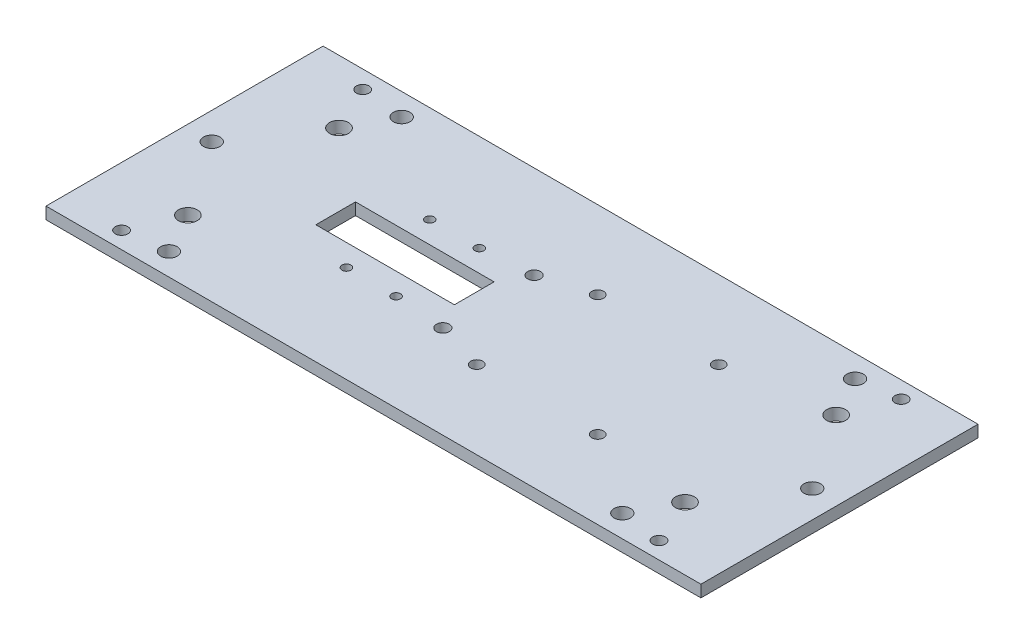
SolidWorks part; units mm, degrees
material "Thornel VCB-20 Carbon Cloth"
ref_plane "Front Plane" through (0, 0, 0) normal (0, 0, 1) x (1, 0, 0)
ref_plane "Top Plane" through (0, 0, 0) normal (0, 1, 0) x (1, 0, 0)
ref_plane "Right Plane" through (0, 0, 0) normal (1, 0, 0) x (0, 0, -1)
sketch "Sketch1" plane through (0, 0, 0) normal (0, 1, 0) x (1, 0, 0)
  line L0 (82.55, -34.925) -> (82.55, 34.925)
  line L1 (82.55, -34.925) -> (-82.55, -34.925)
  line L2 (82.55, 34.925) -> (-82.55, 34.925)
  line L3 (-82.55, -34.925) -> (-82.55, 34.925)
  line L4 (82.55, -34.925) -> (-82.55, 34.925) construction
  line L5 (82.55, 34.925) -> (-82.55, -34.925) construction
  point P1 (0, 0)
  dimension "D1" = 165.1
  dimension "D2" = 69.85
extrude "Boss-Extrude1" add sketch "Sketch1" along normal blind 3
sketch "Sketch6" plane through (0, 0, 0) normal (0, -1, 0) x (1, 0, 0)
  line L0 (-82.55, -34.925) -> (-82.55, 34.925) construction
  line L1 (-44.45, 5) -> (-9.525, 5)
  line L2 (-44.45, 5) -> (-44.45, -5)
  line L3 (-44.45, -5) -> (-9.525, -5)
  line L4 (-9.525, 5) -> (-9.525, -5)
  line L5 (-5.925, -11.501) -> (-63.925, -11.501) construction
  line L6 (-5.925, -11.501) -> (-5.925, 11.501) construction
  line L7 (-5.925, 11.501) -> (-63.925, 11.501) construction
  line L8 (-63.925, -11.501) -> (-63.925, 11.501) construction
  line L9 (-5.925, -11.501) -> (-63.925, 11.501) construction
  line L10 (-5.925, 11.501) -> (-63.925, -11.501) construction
  circle A0 centre (6.35, 15.25) radius 1.5
  circle A1 centre (36.85, 15.25) radius 1.5
  circle A2 centre (6.35, -15.25) radius 1.5
  circle A3 centre (36.85, -15.25) radius 1.5
  circle A4 centre (-63.925, 11.501) radius 1.625 construction
  circle A5 centre (-5.925, 11.501) radius 1.625
  circle A6 centre (-5.925, -11.501) radius 1.625
  circle A7 centre (-63.925, -11.501) radius 1.625 construction
  point P8 (-9.525, 0)
  point P9 (-22.225, 0)
  point P16 (0, 0)
  point P18 (-34.925, 0)
  dimension "D5" = 3
  dimension "D6" = 3
  dimension "D7" = 3
  dimension "D8" = 3
  dimension "D18" = 3.25
  dimension "D1" = 34.925
  dimension "D2" = 10
  dimension "D3" = 38.1
  dimension "D4" = 30.5
  dimension "D9" = 30.5
  dimension "D10" = 30.5
  dimension "D11" = 15.25
  dimension "D12" = 6.35
  dimension "D13" = 15.25
  dimension "D14" = 15.25
  dimension "D15" = 15.25
  dimension "D16" = 23.002
  dimension "D17" = 58
  dimension "D19" = 47.625
  dimension "D20" = 0
extrude "Cut-Extrude1" cut sketch "Sketch6" against normal up to next contours A4 | L4 L1 L2 L3 A4 | A6 | A2 | A3 | A1 | A0 | A7 | A5 region at (-26.9875, 0, 0) region at (6.35, 0, 15.25) region at (36.85, 0, 15.25) region at (6.35, 0, -15.25) region at (36.85, 0, -15.25) region at (-5.925, 0, -11.501)
sketch "Sketch7" plane through (0, 3, 0) normal (0, 1, 0) x (1, 0, 0)
  line L0 (-82.55, 34.925) -> (-82.55, -34.925) construction
  line L1 (82.55, -34.925) -> (82.55, 34.925) construction
  line L2 (-82.55, -34.925) -> (82.55, -34.925) construction
  line L3 (82.55, 34.925) -> (-82.55, 34.925) construction
  circle A0 centre (-77.47, 29.845) radius 1.5
  circle A1 centre (-77.47, -29.845) radius 1.5
  circle A2 centre (77.47, -29.845) radius 1.5
  circle A3 centre (77.47, 29.845) radius 1.5
  dimension "D9" = 3
  dimension "D10" = 3
  dimension "D11" = 3
  dimension "D12" = 3
  dimension "D1" = 5.08
  dimension "D2" = 5.08
  dimension "D3" = 5.08
  dimension "D4" = 5.08
  dimension "D5" = 5.08
  dimension "D6" = 5.08
  dimension "D7" = 5.08
  dimension "D8" = 5.08
sketch "Sketch8" plane through (0, 3, 0) normal (0, 1, 0) x (1, 0, 0)
  line L0 (-82.55, -34.925) -> (82.55, -34.925) construction
  line L1 (-82.55, 34.925) -> (-82.55, -34.925) construction
  line L2 (82.55, -34.925) -> (82.55, 34.925) construction
  line L3 (82.55, 34.925) -> (-82.55, 34.925) construction
  circle A0 centre (-62.6618, -19.05) radius 2.3813
  circle A1 centre (-62.6618, 19.05) radius 2.3813
  circle A2 centre (62.6618, 19.05) radius 2.3813
  circle A3 centre (62.6618, -19.05) radius 2.3813
  dimension "D1" = 4.7625
  dimension "D4" = 4.7625
  dimension "D5" = 4.7625
  dimension "D6" = 4.7625
  dimension "D2" = 15.875
  dimension "D3" = 19.8882
  dimension "D7" = 19.8882
  dimension "D8" = 19.8882
  dimension "D9" = 19.8882
  dimension "D10" = 15.875
  dimension "D11" = 15.875
  dimension "D12" = 15.875
extrude "Cut-Extrude3" cut sketch "Sketch8" against normal up to next
sketch "Sketch9" plane through (0, 3, 0) normal (0, 1, 0) x (1, 0, 0)
  line L0 (-82.55, 34.925) -> (-82.55, -34.925) construction
  line L1 (82.55, -34.925) -> (82.55, 34.925) construction
  circle A0 centre (-75.692, 0) radius 2.0828
  circle A1 centre (75.692, 0) radius 2.0828
  dimension "D1" = 6.858
  dimension "D2" = 6.858
extrude "Cut-Extrude5" cut sketch "Sketch9" against normal blind 5.08
sketch "Sketch10" plane through (0, 3, 0) normal (0, 1, 0) x (1, 0, 0)
  line L0 (-82.55, -34.925) -> (82.55, -34.925) construction
  line L1 (82.55, 34.925) -> (-82.55, 34.925) construction
  circle A0 centre (0, -29.337) radius 2.0828
  circle A1 centre (0, 29.337) radius 2.0828
  circle A2 centre (57.15, -29.337) radius 2.0828
  circle A3 centre (57.15, 29.337) radius 2.0828
  circle A4 centre (-57.15, -29.337) radius 2.0828
  circle A5 centre (-57.15, 29.337) radius 2.0828
  dimension "D1" = 5.588
  dimension "D2" = 5.588
  dimension "D3" = 2
  dimension "D4" = 2
extrude "Cut-Extrude6" cut sketch "Sketch10" against normal blind 5.08 contours A5 | A2 | A3 | A4 region at (57.15, 3, 29.337) region at (57.15, 3, -29.337) region at (-57.15, 3, 29.337) region at (-57.15, 3, -29.337)
sketch "Sketch11" plane through (0, 3, 0) normal (0, 1, 0) x (1, 0, 0)
  line L1 (-18.7375, 10.5) -> (-31.2375, 10.5) construction
  line L2 (-18.7375, 10.5) -> (-18.7375, -10.5) construction
  line L3 (-18.7375, -10.5) -> (-31.2375, -10.5) construction
  line L4 (-31.2375, 10.5) -> (-31.2375, -10.5) construction
  line L5 (-18.7375, 10.5) -> (-31.2375, -10.5) construction
  line L6 (-18.7375, -10.5) -> (-31.2375, 10.5) construction
  line L7 (-9.525, 5) -> (-44.45, 5) construction
  circle A0 centre (-31.2375, 10.5) radius 1.125
  circle A1 centre (-18.7375, 10.5) radius 1.125
  circle A2 centre (-18.7375, -10.5) radius 1.125
  circle A3 centre (-31.2375, -10.5) radius 1.125
  point P0 (-24.9875, 0)
  point P9 (-26.9875, 5)
  dimension "D4" = 2.25
  dimension "D5" = 2.25
  dimension "D6" = 2.25
  dimension "D7" = 2.25
  dimension "D1" = 12.5
  dimension "D2" = 21
  dimension "D3" = 2
extrude "Cut-Extrude7" cut sketch "Sketch11" against normal blind 41.91
sketch "Sketch12" plane through (0, 0, 0) normal (0, -1, 0) x (1, 0, 0)
  line L0 (-24.5963, 23.3735) -> (-5.5463, 23.3735) construction
  line L1 (-24.5963, 24.5641) -> (-5.5463, 24.5641)
  line L2 (-24.5963, 24.5641) -> (-24.5963, 22.1829)
  line L3 (-24.5963, 22.1829) -> (-5.5463, 22.1829)
  line L4 (-5.5463, 24.5641) -> (-5.5463, 22.1829)
  line L5 (-15.0713, 24.5641) -> (-15.0713, 22.1829)
  line L6 (0.8037, 24.5641) -> (0.8037, 22.1829)
  line L7 (0.8037, 24.5641) -> (19.8537, 24.5641)
  line L8 (19.8537, 24.5641) -> (19.8537, 22.1829)
  line L9 (0.8037, 22.1829) -> (19.8537, 22.1829)
  line L10 (26.2037, 24.5641) -> (26.2037, 22.1829)
  line L11 (26.2037, 24.5641) -> (45.2537, 24.5641)
  line L12 (45.2537, 24.5641) -> (45.2537, 22.1829)
  line L13 (26.2037, 22.1829) -> (45.2537, 22.1829)
  line L14 (0.8037, 9.3241) -> (0.8037, 6.9429)
  line L15 (0.8037, 9.3241) -> (19.8537, 9.3241)
  line L16 (19.8537, 9.3241) -> (19.8537, 6.9429)
  line L17 (0.8037, 6.9429) -> (19.8537, 6.9429)
  line L18 (26.2037, 9.3241) -> (26.2037, 6.9429)
  line L19 (26.2037, 9.3241) -> (45.2537, 9.3241)
  line L20 (45.2537, 9.3241) -> (45.2537, 6.9429)
  line L21 (26.2037, 6.9429) -> (45.2537, 6.9429)
  line L22 (-24.5963, 9.3241) -> (-24.5963, 6.9429)
  line L23 (-24.5963, 9.3241) -> (-5.5463, 9.3241)
  line L24 (-5.5463, 9.3241) -> (-5.5463, 6.9429)
  line L25 (-24.5963, 6.9429) -> (-5.5463, 6.9429)
  line L26 (-24.5963, 24.5641) -> (0.8037, 24.5641) construction
  line L27 (-71.2714, 9.2531) -> (-61.3765, 9.2531)
  line L28 (-24.5963, -24.8071) -> (0.8037, -24.8071) construction
  line L29 (-24.5963, -23.6165) -> (-5.5463, -23.6165) construction
  line L30 (-24.5963, -7.1859) -> (-5.5463, -7.1859)
  line L31 (-5.5463, -9.5671) -> (-5.5463, -7.1859)
  line L32 (-24.5963, -9.5671) -> (-5.5463, -9.5671)
  line L33 (-24.5963, -9.5671) -> (-24.5963, -7.1859)
  line L34 (26.2037, -7.1859) -> (45.2537, -7.1859)
  line L35 (45.2537, -9.5671) -> (45.2537, -7.1859)
  line L36 (26.2037, -9.5671) -> (45.2537, -9.5671)
  line L37 (26.2037, -9.5671) -> (26.2037, -7.1859)
  line L38 (0.8037, -7.1859) -> (19.8537, -7.1859)
  line L39 (19.8537, -9.5671) -> (19.8537, -7.1859)
  line L40 (0.8037, -9.5671) -> (19.8537, -9.5671)
  line L41 (0.8037, -9.5671) -> (0.8037, -7.1859)
  line L42 (26.2037, -22.4259) -> (45.2537, -22.4259)
  line L43 (45.2537, -24.8071) -> (45.2537, -22.4259)
  line L44 (26.2037, -24.8071) -> (45.2537, -24.8071)
  line L45 (26.2037, -24.8071) -> (26.2037, -22.4259)
  line L46 (0.8037, -22.4259) -> (19.8537, -22.4259)
  line L47 (19.8537, -24.8071) -> (19.8537, -22.4259)
  line L48 (0.8037, -24.8071) -> (19.8537, -24.8071)
  line L49 (0.8037, -24.8071) -> (0.8037, -22.4259)
  line L50 (-15.0713, -24.8071) -> (-15.0713, -22.4259)
  line L51 (-5.5463, -24.8071) -> (-5.5463, -22.4259)
  line L52 (-24.5963, -22.4259) -> (-5.5463, -22.4259)
  line L53 (-24.5963, -24.8071) -> (-24.5963, -22.4259)
  line L54 (-24.5963, -24.8071) -> (-5.5463, -24.8071)
  line L56 (-3.1651, 10.991) -> (-1.5776, 10.991)
  line L57 (-3.1651, 10.991) -> (-3.1651, 20.516)
  line L58 (-3.1651, 20.516) -> (-1.5776, 20.516)
  line L59 (-1.5776, 10.991) -> (-1.5776, 20.516)
  line L60 (-3.1651, 10.991) -> (-1.5776, 20.516) construction
  line L61 (-3.1651, 20.516) -> (-1.5776, 10.991) construction
  line L66 (-3.1651, -20.759) -> (-1.5776, -20.759)
  line L67 (-1.5776, -11.234) -> (-1.5776, -20.759)
  line L68 (-3.1651, -11.234) -> (-1.5776, -11.234)
  line L69 (-3.1651, -11.234) -> (-3.1651, -20.759)
  line L78 (51.6896, 8.9006) -> (51.6896, 6.5194)
  line L79 (51.6896, 8.9006) -> (70.7396, 8.9006)
  line L80 (70.7396, 8.9006) -> (70.7396, 6.5194)
  line L81 (51.6896, 6.5194) -> (70.7396, 6.5194)
  line L82 (-70.3121, -11.1231) -> (-60.4172, -11.1231)
  line L83 (64.3896, -0.545) -> (-18.1604, -0.545) construction
  line L84 (-70.3121, -11.1231) -> (-70.3121, -9.3903)
  line L85 (51.6896, -7.6094) -> (70.7396, -7.6094)
  line L86 (70.7396, -9.9906) -> (70.7396, -7.6094)
  line L87 (51.6896, -9.9906) -> (70.7396, -9.9906)
  line L88 (51.6896, -9.9906) -> (51.6896, -7.6094)
  line L93 (73.1208, 10.5675) -> (73.1208, 20.0925)
  line L94 (47.7208, 10.5675) -> (49.3083, 10.5675)
  line L95 (47.7208, 10.5675) -> (47.7208, 20.0925)
  line L96 (47.7208, 20.0925) -> (49.3083, 20.0925)
  line L97 (49.3083, 10.5675) -> (49.3083, 20.0925)
  line L98 (47.7208, 10.5675) -> (49.3083, 20.0925) construction
  line L99 (47.7208, 20.0925) -> (49.3083, 10.5675) construction
  line L100 (73.1208, 10.5675) -> (74.7083, 10.5675)
  line L101 (74.7083, 10.5675) -> (74.7083, 20.0925)
  line L102 (73.1208, 20.0925) -> (74.7083, 20.0925)
  line L103 (47.7208, 10.5675) -> (73.1208, 10.5675) construction
  line L104 (47.7208, -21.1825) -> (49.3083, -21.1825)
  line L105 (49.3083, -11.6575) -> (49.3083, -21.1825)
  line L106 (47.7208, -11.6575) -> (49.3083, -11.6575)
  line L107 (47.7208, -11.6575) -> (47.7208, -21.1825)
  line L108 (73.1208, -11.6575) -> (74.7083, -11.6575)
  line L109 (74.7083, -11.6575) -> (74.7083, -21.1825)
  line L110 (73.1208, -21.1825) -> (74.7083, -21.1825)
  line L111 (73.1208, -11.6575) -> (73.1208, -21.1825)
  line L112 (-70.3121, -9.3903) -> (-60.4172, -9.3903)
  line L113 (-60.4172, -11.1231) -> (-60.4172, -9.3903)
  line L114 (-52.8291, -27.8715) -> (-33.7791, -27.8715)
  line L115 (-33.7791, -30.2527) -> (-33.7791, -27.8715)
  line L116 (-52.8291, -30.2527) -> (-33.7791, -30.2527)
  line L117 (-52.8291, -30.2527) -> (-52.8291, -27.8715)
  line L118 (-70.3121, -11.1231) -> (-60.4172, -9.3903) construction
  line L123 (-59.3265, -23.1262) -> (-57.739, -23.1262)
  line L124 (-57.739, -13.6012) -> (-57.739, -23.1262)
  line L125 (-59.3265, -13.6012) -> (-57.739, -13.6012)
  line L126 (-59.3265, -13.6012) -> (-59.3265, -23.1262)
  line L127 (-31.3979, -16.6796) -> (-29.8104, -16.6796)
  line L128 (-29.8104, -16.6796) -> (-29.8104, -26.2046)
  line L129 (-31.3979, -26.2046) -> (-29.8104, -26.2046)
  line L130 (-31.3979, -16.6796) -> (-31.3979, -26.2046)
  line L131 (-70.3121, -9.3903) -> (-60.4172, -11.1231) construction
  line L132 (-71.2714, 9.2531) -> (-71.2714, 10.9859)
  line L133 (-31.3979, 16.4366) -> (-31.3979, 25.9616)
  line L134 (-31.3979, 25.9616) -> (-29.8104, 25.9616)
  line L135 (-29.8104, 16.4366) -> (-29.8104, 25.9616)
  line L136 (-31.3979, 16.4366) -> (-29.8104, 16.4366)
  line L137 (-59.5464, 13.798) -> (-59.5464, 23.323)
  line L138 (-59.5464, 13.798) -> (-57.9589, 13.798)
  line L139 (-57.9589, 13.798) -> (-57.9589, 23.323)
  line L140 (-59.5464, 23.323) -> (-57.9589, 23.323)
  line L145 (-71.2714, 10.9859) -> (-61.3765, 10.9859)
  line L146 (-52.8291, 30.0097) -> (-52.8291, 27.6285)
  line L147 (-52.8291, 30.0097) -> (-33.7791, 30.0097)
  line L148 (-33.7791, 30.0097) -> (-33.7791, 27.6285)
  line L149 (-52.8291, 27.6285) -> (-33.7791, 27.6285)
  line L150 (-61.3765, 9.2531) -> (-61.3765, 10.9859)
  point P8 (-65.3646, -10.2567)
  point P60 (-2.3713, 15.7535)
  point P100 (48.5146, 15.33)
  dimension "D1" = 19.05
  dimension "D2" = 2.3813
  dimension "D3" = 25.4
  dimension "D4" = 15.24
  dimension "D5" = 1.5875
  dimension "D6" = 3.175
  dimension "D7" = 9.525
  dimension "D8" = 7.62
extrude "Cut-Extrude8" [suppressed] cut sketch "Sketch12" against normal blind 21.336 contours L37 L36 L35 L34 | L88 L87 L86 L85 | L45 L44 L43 L42 | L117 L116 L115 L114 | L78 L81 L80 L79 | L10 L13 L12 L11 | L6 L9 L8 L7 | L14 L17 L16 L15 | L107 L104 L105 L106 | L109 L110 L111 L108 | L40 L39 L38 L41 | L48 L47 L46 L49 | L67 L66 L69 L68 | L52 L51 L54 L53 | L30 L31 L32 L33 | L130 L129 L128 L127 | L126 L123 L124 L125 | L93 L102 L101 L100 | L97 L96 L95 L94 | L19 L20 L21 L18 | L56 L59 L58 L57 | L25 L24 L23 L22 | L3 L4 L1 L2 | L135 L134 L133 L136 | L149 L148 L147 L146 | L139 L140 L137 L138 | L27 L150 L145 L132 | L84 L82 L113 L112
sketch "Sketch13" plane through (0, 0, 0) normal (0, -1, 0) x (1, 0, 0)
  line L0 (0, 18.4306) -> (0, -15.755) construction
  line L2 (-82.55, 34.925) -> (82.55, 34.925) construction
  circle A0 centre (-62.6618, 19.05) radius 2.3813 construction
  circle A6 centre (-67.7422, 30.6896) radius 1.5875
  circle A12 centre (67.7422, 30.6896) radius 1.5875
  circle A13 centre (67.412, -30.6896) radius 1.5875
  circle A14 centre (-68.0721, -30.4405) radius 1.5875
  point P17 (0.9735, -0.4356)
  point P19 (-0.1369, 0.0621)
  dimension "D2" = 3.175
  dimension "D1" = 12.7
  dimension "D3" = 2
  dimension "D4" = 4.2354
extrude "Cut-Extrude9" cut sketch "Sketch13" against normal blind 5
